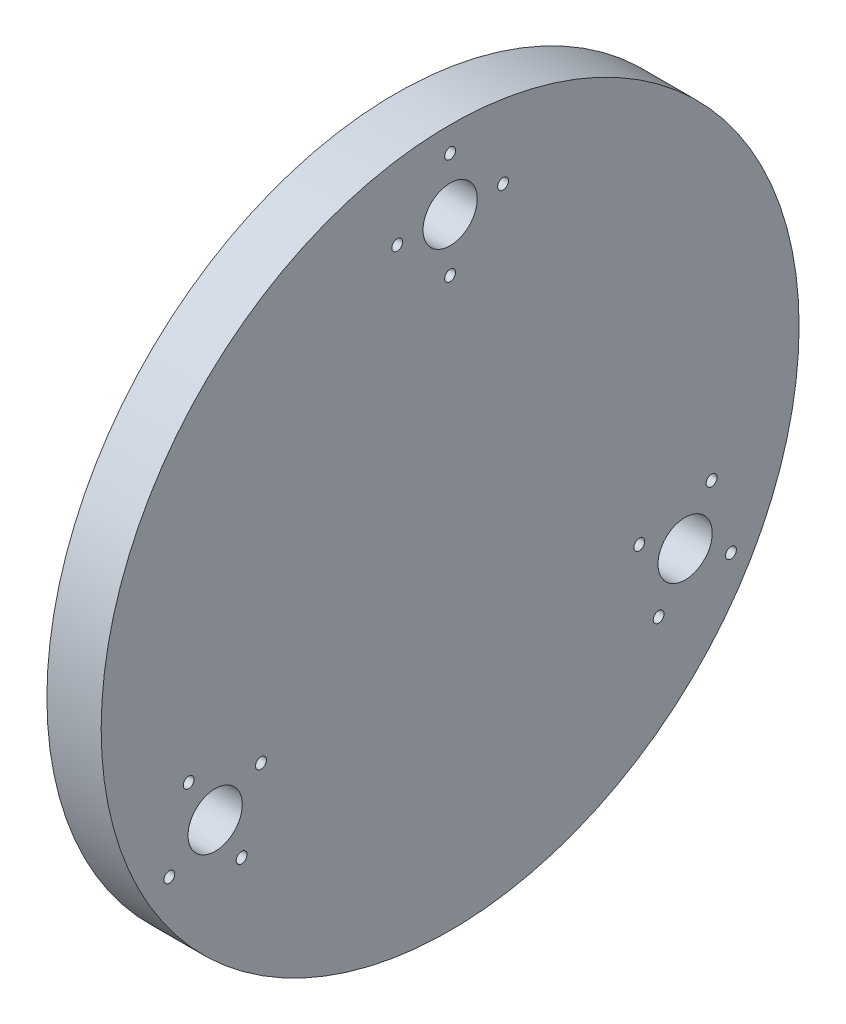
SolidWorks part; units mm, degrees
ref_plane "Front Plane" through (0, 0, 0) normal (0, 0, 1) x (1, 0, 0)
ref_plane "Top Plane" through (0, 0, 0) normal (0, 1, 0) x (1, 0, 0)
ref_plane "Right Plane" through (0, 0, 0) normal (1, 0, 0) x (0, 0, -1)
sketch "Sketch1" plane through (0, 0, 0) normal (1, 0, 0) x (0, 0, -1)
  line L0 (-72.7, 0) -> (72.7, 0) construction
  line L1 (-9.75, 50) -> (9.75, 50) construction
  line L2 (0, 40.25) -> (0, 59.75) construction
  circle A0 centre (51.745, -29.875) radius 1
  circle A1 centre (0, 50) radius 5
  circle A2 centre (48.1763, -16.5563) radius 1
  circle A3 centre (43.3013, -25) radius 5
  circle A4 centre (0, 0) radius 64.3086
  circle A5 centre (0, 59.75) radius 1
  circle A6 centre (9.75, 50) radius 1
  circle A7 centre (0, 40.25) radius 1
  circle A8 centre (-9.75, 50) radius 1
  circle A9 centre (38.4263, -33.4437) radius 1
  circle A10 centre (34.8575, -20.125) radius 1
  circle A11 centre (-51.745, -29.875) radius 1
  circle A12 centre (-38.4263, -33.4437) radius 1
  circle A13 centre (-43.3013, -25) radius 5
  circle A14 centre (-48.1763, -16.5563) radius 1
  circle A15 centre (-34.8575, -20.125) radius 1
  point P5 (-9.2055, 50)
  point P11 (0, 0)
  point P24 (0, 48.85)
  point P39 (0, 0)
  point P40 (10.7041, 50)
  point P41 (0, 41.25)
  point P42 (0, 63.5355)
  point P43 (0, 33.844)
  point P44 (-19.6102, 49.85)
  point P45 (0, 0)
  point P46 (0, 0)
  point P47 (9.7041, 50)
  point P48 (0, 59.75)
  point P49 (0, 0)
  point P50 (0, 60.75)
  dimension "D1" = 50
  dimension "D3" = 19.5
  dimension "D4" = 10
  dimension "D5" = 2
  dimension "D2" = 3
extrude "Boss-Extrude2" add sketch "Sketch1" along normal blind 10
